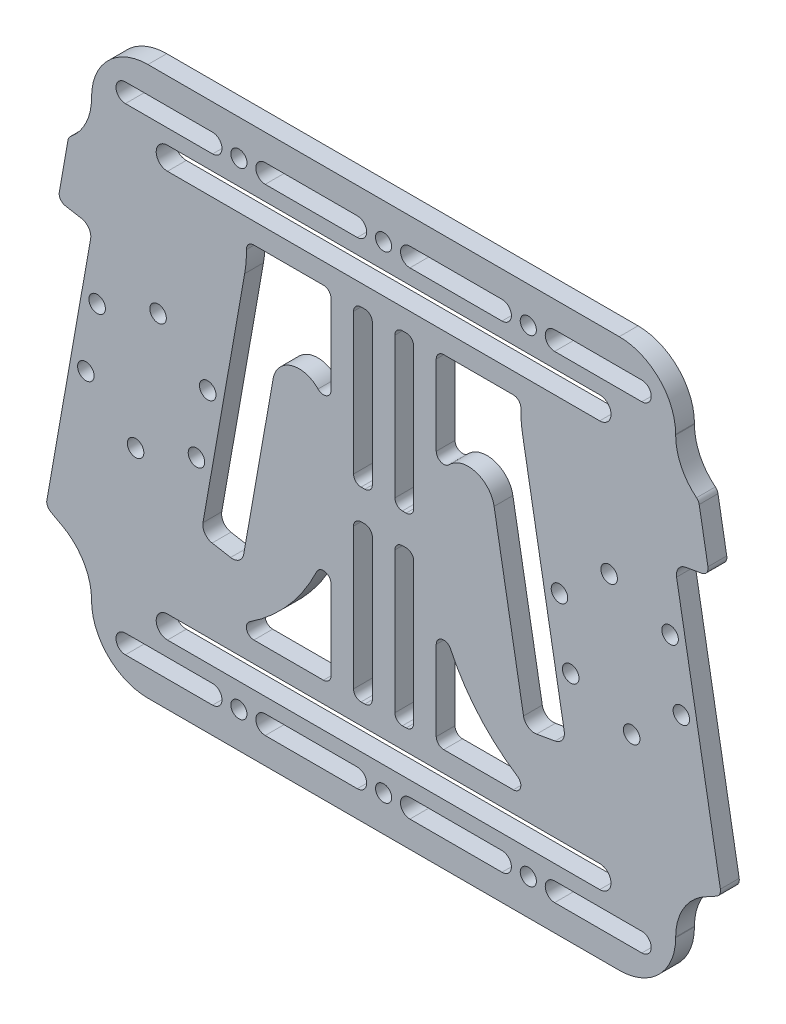
SolidWorks part; units mm, degrees
ref_plane "前视基准面" through (0, 0, 0) normal (0, 0, 1) x (1, 0, 0)
ref_plane "上视基准面" through (0, 0, 0) normal (0, 1, 0) x (1, 0, 0)
ref_plane "右视基准面" through (0, 0, 0) normal (1, 0, 0) x (0, 0, -1)
other "Configuration Table"
sketch "草图1" plane through (0, 0, 0) normal (0, 0, 1) x (1, 0, 0)
  line L0 (0, 0) -> (126, 0) construction
  line L1 (0, 86) -> (126, 86)
  line L2 (0, -86) -> (126, -86)
  line L3 (63, 86) -> (63, -86) construction
  arc A0 (0, 86) -> (0, -86) centre (0, 0) ccw
  arc A1 (126, -86) -> (126, 86) centre (126, 0) ccw
  circle A2 centre (0, 0) radius 44.5 construction
  circle A3 centre (126, 0) radius 44.5 construction
  circle A4 centre (0, 0) radius 42.5 construction
  circle A5 centre (126, 0) radius 42.5 construction
  circle A6 centre (0, 44.5) radius 1.9
  circle A7 centre (31.4663, 31.4663) radius 1.9
  circle A8 centre (44.5, 0) radius 1.9
  circle A9 centre (31.4663, -31.4663) radius 1.9
  circle A10 centre (0, -44.5) radius 1.9
  circle A11 centre (-31.4663, -31.4663) radius 1.9
  circle A12 centre (-44.5, 0) radius 1.9
  circle A13 centre (-31.4663, 31.4663) radius 1.9
  circle A14 centre (-42.5, 0) radius 1.9
  circle A15 centre (42.5, 0) radius 1.9
  circle A16 centre (168.5, 0) radius 1.9
  circle A17 centre (83.5, 0) radius 1.9
  circle A18 centre (94.5337, -31.4663) radius 1.9
  circle A19 centre (126, -44.5) radius 1.9
  circle A20 centre (157.4663, -31.4663) radius 1.9
  circle A21 centre (94.5337, 31.4663) radius 1.9
  circle A22 centre (126, 44.5) radius 1.9
  circle A23 centre (157.4663, 31.4663) radius 1.9
  circle A24 centre (0, 0) radius 31
  circle A25 centre (126, 0) radius 31
  circle A26 centre (126, 42.5) radius 1.9
  circle A27 centre (126, -42.5) radius 1.9
  circle A28 centre (0, -42.5) radius 1.9
  circle A29 centre (0, 42.5) radius 1.9
  circle A30 centre (170.5, 0) radius 1.9
  circle A31 centre (81.5, 0) radius 1.9
  point P3 (63, 0)
  point P33 (0, 0)
  dimension "D1" = 86
  dimension "D3" = 89
  dimension "D4" = 89
  dimension "D5" = 85
  dimension "D6" = 85
  dimension "D7" = 3.8
  dimension "D10" = 3.8
  dimension "D11" = 62
  dimension "D2" = 126
  dimension "D9" = 45
  dimension "D8" = 8
extrude "凸台-拉伸1" add sketch "草图1" along normal blind 5 contours L2 A1 L1 A0 A25 A24 A22 A20 A18 A16 A15 A8 A14 A12 A13 A11 A10 A9 A7 A6 A17 A19 A21 A23 | A15 A8 | A14 A12 region at (63, 0, 0) region at (45.068, 0, 0) region at (-45.068, 0, 0)
sketch "草图3" plane through (0, 0, 5) normal (0, 0, 1) x (1, 0, 0)
  line L0 (13, 41) -> (113, 41)
  line L1 (63, 86) -> (63, -86) construction
  line L2 (13, 41) -> (13, 86)
  line L3 (113, 41) -> (113, 86)
  line L4 (13, 63.5) -> (113, 63.5) construction
  line L5 (0, -86) -> (126, -86)
  line L6 (-86, 0) -> (212, 0) construction
  line L7 (126, 86) -> (0, 86)
  line L9 (0, -86) -> (126, -86)
  line L11 (126, 86) -> (0, 86)
  circle A0 centre (63, 63.5) radius 2.15
  circle A1 centre (101.5, 63.5) radius 2.15
  circle A2 centre (24.5, 63.5) radius 2.15
  circle A3 centre (101.5, -63.5) radius 2.15
  circle A4 centre (63, -63.5) radius 2.15
  circle A5 centre (24.5, -63.5) radius 2.15
  arc A8 (0, 86) -> (0, -86) centre (0, 0) ccw
  arc A12 (126, -86) -> (126, 86) centre (126, 0) ccw
  arc A16 (0, 86) -> (0, -86) centre (0, 0) ccw
  arc A20 (126, -86) -> (126, 86) centre (126, 0) ccw
  dimension "D4" = 4.3
  dimension "D6" = 4.3
  dimension "D2" = 45
  dimension "D3" = 100
  dimension "D5" = 77
  dimension "D1" = 0
extrude "切除-拉伸2" cut sketch "草图3" against normal blind 366 contours A2 | A0 | A1 | A5 | A4 | A3 region at (63, 63.5, 5) region at (101.5, 63.5, 5) region at (24.5, 63.5, 5) region at (101.5, -63.5, 5) region at (63, -63.5, 5) region at (24.5, -63.5, 5)
sketch "草图4" plane through (0, 0, 5) normal (0, 0, 1) x (1, 0, 0)
  line L0 (-15.1381, 73) -> (141.1381, 73)
  line L1 (63, 86) -> (63, -86) construction
  line L2 (0, -86) -> (126, -86)
  line L3 (126, 86) -> (0, 86)
  line L4 (0, -86) -> (126, -86)
  line L5 (126, 86) -> (0, 86)
  line L6 (-86, 0) -> (212, 0) construction
  line L7 (-15.1381, 73) -> (-64, 32)
  line L8 (-64, 32) -> (-64, -32)
  line L9 (-15.1381, -73) -> (141.1381, -73)
  line L10 (-15.1381, -73) -> (-64, -32)
  line L11 (141.1381, -73) -> (190, -32)
  line L12 (141.1381, 73) -> (190, 32)
  line L13 (190, 32) -> (190, -32)
  circle A0 centre (63, 63.5) radius 2.15 construction
  arc A2 (126, -86) -> (126, 86) centre (126, 0) ccw
  arc A3 (0, 86) -> (0, -86) centre (0, 0) ccw
  arc A4 (126, -86) -> (126, 86) centre (126, 0) ccw
  arc A5 (0, 86) -> (0, -86) centre (0, 0) ccw
  point P20 (-64, 0)
  dimension "D2" = 9.5
  dimension "D3" = 140
  dimension "D4" = 22
  dimension "D5" = 32
  dimension "D1" = 0
extrude "切除-拉伸3" cut sketch "草图4" against normal blind 366 contours L4 A4 L5 A5 | L11 L13 L12 L0 L7 L8 L10 L9
fillet "圆角2" radius 20 4 edges at (-15.1381, -73, 2.5) (141.1381, -73, 2.5) (141.1381, 73, 2.5) (-15.1381, 73, 2.5)
fillet "圆角3" radius 35 4 edges at (190, -32, 2.5) (190, 32, 2.5) (-64, -32, 2.5) (-64, 32, 2.5)
sketch "草图8" plane through (0, 0, 5) normal (0, 0, 1) x (1, 0, 0)
  line L2 (126, 86) -> (0, 86)
  line L3 (0, -86) -> (126, -86)
  line L4 (126, 86) -> (0, 86)
  line L5 (0, -86) -> (126, -86)
  arc A0 (169.5, -1.6155) -> (169.5, 1.6155) centre (170.5, 0) ccw construction
  circle A1 centre (0, 44.5) radius 1.9
  circle A2 centre (0, 44.5) radius 1.9
  circle A3 centre (-42.5, 0) radius 1.9
  arc A4 (126, -86) -> (126, 86) centre (126, 0) ccw
  arc A5 (0, 86) -> (0, -86) centre (0, 0) ccw
  arc A6 (126, -86) -> (126, 86) centre (126, 0) ccw
  arc A7 (0, 86) -> (0, -86) centre (0, 0) ccw
  circle A8 centre (-42.5, 0) radius 1.9
  circle A9 centre (-44.5, 0) radius 1.9
  circle A10 centre (-44.5, 0) radius 1.9
  circle A11 centre (-31.4663, -31.4663) radius 1.9
  circle A12 centre (-31.4663, -31.4663) radius 1.9
  circle A13 centre (0, -44.5) radius 1.9
  circle A14 centre (0, -44.5) radius 1.9
  circle A15 centre (31.4663, -31.4663) radius 1.9
  circle A16 centre (31.4663, -31.4663) radius 1.9
  circle A17 centre (44.5, 0) radius 1.9
  circle A18 centre (44.5, 0) radius 1.9
  circle A19 centre (31.4663, 31.4663) radius 1.9
  circle A20 centre (31.4663, 31.4663) radius 1.9
  circle A21 centre (157.4663, -31.4663) radius 1.9
  circle A22 centre (157.4663, -31.4663) radius 1.9
  circle A23 centre (126, -44.5) radius 1.9
  circle A24 centre (126, -44.5) radius 1.9
  circle A25 centre (94.5337, -31.4663) radius 1.9
  circle A26 centre (94.5337, -31.4663) radius 1.9
  circle A27 centre (83.5, 0) radius 1.9
  circle A28 centre (83.5, 0) radius 1.9
  circle A29 centre (168.5, 0) radius 1.9
  circle A30 centre (168.5, 0) radius 1.9
  circle A31 centre (42.5, 0) radius 1.9
  circle A32 centre (42.5, 0) radius 1.9
  circle A33 centre (-31.4663, 31.4663) radius 1.9
  circle A34 centre (-31.4663, 31.4663) radius 1.9
  circle A35 centre (0, -42.5) radius 1.9
  circle A36 centre (0, -42.5) radius 1.9
  circle A37 centre (126, -42.5) radius 1.9
  circle A38 centre (126, -42.5) radius 1.9
  circle A39 centre (126, 42.5) radius 1.9
  circle A40 centre (126, 42.5) radius 1.9
  circle A41 centre (126, 0) radius 31
  circle A42 centre (126, 0) radius 31
  circle A43 centre (0, 0) radius 31
  circle A44 centre (0, 0) radius 31
  circle A45 centre (157.4663, 31.4663) radius 1.9
  circle A46 centre (157.4663, 31.4663) radius 1.9
  circle A47 centre (126, 44.5) radius 1.9
  circle A48 centre (126, 44.5) radius 1.9
  circle A49 centre (94.5337, 31.4663) radius 1.9
  circle A50 centre (94.5337, 31.4663) radius 1.9
  circle A51 centre (0, 42.5) radius 1.9
  circle A52 centre (0, 42.5) radius 1.9
  arc A53 (82.5, 1.6155) -> (82.5, -1.6155) centre (81.5, 0) ccw construction
  arc A54 (169.5, -1.6155) -> (169.5, 1.6155) centre (170.5, 0) ccw
  arc A55 (82.5, 1.6155) -> (82.5, -1.6155) centre (81.5, 0) ccw
  circle A56 centre (81.5, 0) radius 1.9
  circle A57 centre (170.5, 0) radius 1.9
  dimension "D1" = 0
  dimension "D2" = 0
  dimension "D3" = 0
  dimension "D4" = 0
  dimension "D5" = 0
  dimension "D6" = 0
  dimension "D7" = 0
  dimension "D8" = 0
  dimension "D9" = 0
  dimension "D10" = 0
  dimension "D11" = 0
  dimension "D12" = 0
  dimension "D13" = 0
  dimension "D14" = 0
  dimension "D15" = 0
  dimension "D16" = 0
  dimension "D17" = 0
  dimension "D18" = 0
  dimension "D19" = 0
  dimension "D20" = 0
  dimension "D21" = 0
  dimension "D22" = 0
  dimension "D23" = 0
  dimension "D24" = 0
  dimension "D25" = 0
extrude "凸台-拉伸5" add sketch "草图8" against normal blind 5 contours A52 A2 | A36 A14 | A18 A32 | A10 A8 | A40 A48 | A38 A24 | A57 A30 | A56 A28 region at (0, 45.068, 5) region at (-41.932, 0, 5) region at (0, -45.068, 5) region at (41.932, 0, 5) region at (126, -45.068, 5) region at (84.068, 0, 5) region at (167.932, 0, 5) region at (126, 45.068, 5)
sketch "草图9" plane through (0, 0, 5) normal (0, 0, 1) x (1, 0, 0)
  line L2 (126, 86) -> (0, 86)
  line L3 (0, -86) -> (126, -86)
  line L4 (126, 86) -> (0, 86)
  line L5 (0, -86) -> (126, -86)
  arc A0 (169.5, -1.6155) -> (169.5, 1.6155) centre (170.5, 0) ccw construction
  circle A1 centre (-42.5, 0) radius 1.9
  circle A2 centre (-42.5, 0) radius 1.9
  circle A3 centre (0, 44.5) radius 1.9
  circle A4 centre (0, 44.5) radius 1.9
  circle A5 centre (31.4663, 31.4663) radius 1.9
  arc A6 (0, 86) -> (0, -86) centre (0, 0) ccw
  arc A7 (126, -86) -> (126, 86) centre (126, 0) ccw
  arc A8 (0, 86) -> (0, -86) centre (0, 0) ccw
  arc A9 (126, -86) -> (126, 86) centre (126, 0) ccw
  circle A10 centre (31.4663, 31.4663) radius 1.9
  circle A11 centre (44.5, 0) radius 1.9
  circle A12 centre (44.5, 0) radius 1.9
  circle A13 centre (31.4663, -31.4663) radius 1.9
  circle A14 centre (31.4663, -31.4663) radius 1.9
  circle A15 centre (0, -44.5) radius 1.9
  circle A16 centre (0, -44.5) radius 1.9
  circle A17 centre (-31.4663, -31.4663) radius 1.9
  circle A18 centre (-31.4663, -31.4663) radius 1.9
  circle A19 centre (-44.5, 0) radius 1.9
  circle A20 centre (-44.5, 0) radius 1.9
  circle A21 centre (168.5, 0) radius 1.9
  circle A22 centre (168.5, 0) radius 1.9
  circle A23 centre (83.5, 0) radius 1.9
  circle A24 centre (83.5, 0) radius 1.9
  circle A25 centre (94.5337, -31.4663) radius 1.9
  circle A26 centre (94.5337, -31.4663) radius 1.9
  circle A27 centre (126, -44.5) radius 1.9
  circle A28 centre (126, -44.5) radius 1.9
  circle A29 centre (157.4663, -31.4663) radius 1.9
  circle A30 centre (157.4663, -31.4663) radius 1.9
  circle A31 centre (126, 42.5) radius 1.9
  circle A32 centre (126, 42.5) radius 1.9
  circle A33 centre (126, -42.5) radius 1.9
  circle A34 centre (126, -42.5) radius 1.9
  circle A35 centre (0, -42.5) radius 1.9
  circle A36 centre (0, -42.5) radius 1.9
  circle A37 centre (-31.4663, 31.4663) radius 1.9
  circle A38 centre (-31.4663, 31.4663) radius 1.9
  circle A39 centre (42.5, 0) radius 1.9
  circle A40 centre (42.5, 0) radius 1.9
  circle A41 centre (0, 42.5) radius 1.9
  circle A42 centre (0, 42.5) radius 1.9
  circle A43 centre (94.5337, 31.4663) radius 1.9
  circle A44 centre (94.5337, 31.4663) radius 1.9
  circle A45 centre (126, 44.5) radius 1.9
  circle A46 centre (126, 44.5) radius 1.9
  circle A47 centre (157.4663, 31.4663) radius 1.9
  circle A48 centre (157.4663, 31.4663) radius 1.9
  circle A49 centre (0, 0) radius 31
  circle A50 centre (0, 0) radius 31
  circle A51 centre (126, 0) radius 31
  circle A52 centre (126, 0) radius 31
  circle A53 centre (170.5, 0) radius 1.9
  circle A54 centre (170.5, 0) radius 1.9
  circle A55 centre (81.5, 0) radius 1.9
  circle A56 centre (81.5, 0) radius 1.9
  arc A57 (82.5, 1.6155) -> (82.5, -1.6155) centre (81.5, 0) ccw construction
  arc A58 (169.5, -1.6155) -> (169.5, 1.6155) centre (170.5, 0) ccw
  arc A59 (82.5, 1.6155) -> (82.5, -1.6155) centre (81.5, 0) ccw
  dimension "D1" = 0
  dimension "D2" = 0
  dimension "D3" = 0
  dimension "D4" = 0
  dimension "D5" = 0
  dimension "D6" = 0
  dimension "D7" = 0
  dimension "D8" = 0
  dimension "D9" = 0
  dimension "D10" = 0
  dimension "D11" = 0
  dimension "D12" = 0
  dimension "D13" = 0
  dimension "D14" = 0
  dimension "D15" = 0
  dimension "D16" = 0
  dimension "D17" = 0
  dimension "D18" = 0
  dimension "D19" = 0
  dimension "D20" = 0
  dimension "D21" = 0
  dimension "D22" = 0
  dimension "D23" = 0
  dimension "D24" = 0
  dimension "D25" = 0
  dimension "D26" = 0
  dimension "D27" = 0
extrude "切除-拉伸6" cut sketch "草图9" against normal blind 5 contours A20 A2 | A12 A40 region at (-41.932, 0, 5) region at (41.932, 0, 5)
sketch "草图11" plane through (0, 0, 0) normal (0, 0, -1) x (-1, 0, 0)
  line L0 (-63, 73) -> (-63, -73) construction
  line L1 (-140.6991, 71.7939) -> (-140.6991, 47.7905)
  line L2 (-190, 0) -> (64, 0) construction
  line L3 (14.6991, 71.7939) -> (14.6991, 47.7905)
  line L4 (14.6991, -71.7939) -> (14.6991, -47.7905)
  line L5 (-140.6991, -71.7939) -> (-140.6991, -47.7905)
  line L8 (-190, 15.6792) -> (-190, -15.6792)
  line L9 (-177.4976, -42.4908) -> (-146.7145, -68.3209)
  line L10 (-133.8587, -73) -> (7.8587, -73)
  line L11 (20.7145, -68.3209) -> (51.4976, -42.4908)
  line L12 (64, -15.6792) -> (64, 15.6792)
  line L13 (51.4976, 42.4908) -> (20.7145, 68.3209)
  line L14 (7.8587, 73) -> (-133.8587, 73)
  line L15 (-146.7145, 68.3209) -> (-177.4976, 42.4908)
  line L16 (-190, 15.6792) -> (-190, -15.6792)
  line L17 (-177.4976, -42.4908) -> (-146.7145, -68.3209)
  line L18 (-133.8587, -73) -> (7.8587, -73)
  line L19 (20.7145, -68.3209) -> (51.4976, -42.4908)
  line L20 (64, -15.6792) -> (64, 15.6792)
  line L21 (51.4976, 42.4908) -> (20.7145, 68.3209)
  line L22 (7.8587, 73) -> (-133.8587, 73)
  line L23 (-146.7145, 68.3209) -> (-177.4976, 42.4908)
  circle A0 centre (-126, 0) radius 50
  circle A1 centre (0, 0) radius 50
  arc A8 (-190, -15.6792) -> (-177.4976, -42.4908) centre (-155, -15.6792) ccw
  arc A9 (-146.7145, -68.3209) -> (-133.8587, -73) centre (-133.8587, -53) ccw
  arc A10 (7.8587, -73) -> (20.7145, -68.3209) centre (7.8587, -53) ccw
  arc A11 (51.4976, -42.4908) -> (64, -15.6792) centre (29, -15.6792) ccw
  arc A12 (64, 15.6792) -> (51.4976, 42.4908) centre (29, 15.6792) ccw
  arc A13 (20.7145, 68.3209) -> (7.8587, 73) centre (7.8587, 53) ccw
  arc A14 (-133.8587, 73) -> (-146.7145, 68.3209) centre (-133.8587, 53) ccw
  arc A15 (-177.4976, 42.4908) -> (-190, 15.6792) centre (-155, 15.6792) ccw
  arc A16 (-190, -15.6792) -> (-177.4976, -42.4908) centre (-155, -15.6792) ccw
  arc A17 (-146.7145, -68.3209) -> (-133.8587, -73) centre (-133.8587, -53) ccw
  arc A18 (7.8587, -73) -> (20.7145, -68.3209) centre (7.8587, -53) ccw
  arc A19 (51.4976, -42.4908) -> (64, -15.6792) centre (29, -15.6792) ccw
  arc A20 (64, 15.6792) -> (51.4976, 42.4908) centre (29, 15.6792) ccw
  arc A21 (20.7145, 68.3209) -> (7.8587, 73) centre (7.8587, 53) ccw
  arc A22 (-133.8587, 73) -> (-146.7145, 68.3209) centre (-133.8587, 53) ccw
  arc A23 (-177.4976, 42.4908) -> (-190, 15.6792) centre (-155, 15.6792) ccw
  dimension "D2" = 100
  dimension "D1" = 0
extrude "切除-拉伸7" cut sketch "草图11" against normal blind 5 contours L23 A23 L16 A16 L17 A17 L5 A0 L1 A22 | L21 A21 L3 A1 L4 A18 L19 A19 L20 A20 region at (142.2173, 59.7922, 0) region at (-17.0996, 69.0057, 0)
fillet "圆角6" radius 15 4 edges at (140.6991, 71.7939, 2.5) (-14.6991, 71.7939, 2.5) (140.6991, -71.7939, 2.5) (-14.6991, -71.7939, 2.5)
sketch "草图14" plane through (0, 0, 5) normal (0, 0, 1) x (1, 0, 0)
  line L0 (24.5, 63.5) -> (101.3352, 63.5) construction
  line L1 (-5.6991, 63.5) -> (17.5, 63.5) construction
  line L2 (-5.6991, 66) -> (17.5, 66)
  line L3 (-5.6991, 61) -> (17.5, 61)
  line L4 (31.5, 63.5) -> (56, 63.5) construction
  line L5 (31.5, 66) -> (56, 66)
  line L6 (140.6991, 47.7905) -> (140.6991, 58)
  line L7 (125.6991, 73) -> (0.3009, 73)
  line L8 (-14.6991, 58) -> (-14.6991, 47.7905)
  line L9 (-14.6991, -47.7905) -> (-14.6991, -58)
  line L10 (0.3009, -73) -> (125.6991, -73)
  line L11 (140.6991, -58) -> (140.6991, -47.7905)
  line L12 (140.6991, 47.7905) -> (140.6991, 58)
  line L13 (125.6991, 73) -> (0.3009, 73)
  line L14 (-14.6991, 58) -> (-14.6991, 47.7905)
  line L15 (-14.6991, -47.7905) -> (-14.6991, -58)
  line L16 (0.3009, -73) -> (125.6991, -73)
  line L17 (140.6991, -58) -> (140.6991, -47.7905)
  line L18 (31.5, 61) -> (56, 61)
  line L19 (94.5, 63.5) -> (70, 63.5) construction
  line L22 (94.5, 66) -> (70, 66)
  line L25 (63, 73) -> (63, -73) construction
  line L26 (94.5, 61) -> (70, 61)
  line L27 (131.6991, 63.5) -> (108.5, 63.5) construction
  line L28 (131.6991, 66) -> (108.5, 66)
  line L29 (131.6991, 61) -> (108.5, 61)
  line L30 (5.5, 54) -> (120.5, 54) construction
  line L31 (5.5, 57) -> (120.5, 57)
  line L32 (5.5, 51) -> (120.5, 51)
  circle A0 centre (24.5, 63.5) radius 2.15 construction
  circle A1 centre (24.5, 63.5) radius 2.15
  arc A2 (-5.6991, 66) -> (-5.6991, 61) centre (-5.6991, 63.5) ccw
  arc A3 (17.5, 61) -> (17.5, 66) centre (17.5, 63.5) ccw
  arc A4 (31.5, 66) -> (31.5, 61) centre (31.5, 63.5) ccw
  arc A5 (56, 61) -> (56, 66) centre (56, 63.5) ccw
  arc A10 (140.6991, 58) -> (125.6991, 73) centre (125.6991, 58) ccw
  arc A11 (0.3009, 73) -> (-14.6991, 58) centre (0.3009, 58) ccw
  arc A13 (-14.6991, 47.7905) -> (-14.6991, -47.7905) centre (0, 0) ccw
  arc A15 (-14.6991, -58) -> (0.3009, -73) centre (0.3009, -58) ccw
  arc A16 (125.6991, -73) -> (140.6991, -58) centre (125.6991, -58) ccw
  arc A20 (140.6991, 58) -> (125.6991, 73) centre (125.6991, 58) ccw
  arc A21 (0.3009, 73) -> (-14.6991, 58) centre (0.3009, 58) ccw
  arc A25 (-14.6991, -58) -> (0.3009, -73) centre (0.3009, -58) ccw
  arc A26 (125.6991, -73) -> (140.6991, -58) centre (125.6991, -58) ccw
  circle A30 centre (63, 63.5) radius 2.15 construction
  arc A31 (94.5, 66) -> (94.5, 61) centre (94.5, 63.5) cw
  arc A32 (70, 61) -> (70, 66) centre (70, 63.5) cw
  arc A33 (131.6991, 66) -> (131.6991, 61) centre (131.6991, 63.5) cw
  arc A34 (108.5, 61) -> (108.5, 66) centre (108.5, 63.5) cw
  arc A35 (5.5, 57) -> (5.5, 51) centre (5.5, 54) ccw
  arc A36 (120.5, 51) -> (120.5, 57) centre (120.5, 54) ccw
  arc A42 (-14.6991, 47.7905) -> (-14.6991, -47.7905) centre (0, 0) ccw
  arc A43 (140.6991, -47.7905) -> (140.6991, 47.7905) centre (126, 0) ccw
  arc A44 (140.6991, -47.7905) -> (140.6991, 47.7905) centre (126, 0) ccw
  point P23 (5.9004, 63.5)
  point P37 (43.75, 63.5)
  point P46 (63, 54)
  point P52 (82.25, 63.5)
  point P59 (120.0996, 63.5)
  dimension "D2" = 9
  dimension "D7" = 7
  dimension "D8" = 3
  dimension "D10" = 115
  dimension "D3" = 7
  dimension "D4" = 7
  dimension "D5" = 7
  dimension "D6" = 7
  dimension "D9" = 4
  dimension "D1" = 0
extrude "切除-拉伸8" cut sketch "草图14" against normal blind 10 contours L3 A3 L2 A2 | L32 A36 L31 A35 | L18 A5 L5 A4 | L22 A32 L26 A31 | L28 A34 L29 A33
sketch "草图5" plane through (0, 0, 5) normal (0, 0, 1) x (1, 0, 0)
  line L0 (63, 73) -> (63, -73) construction
  line L1 (55, 45.5) -> (55, 4)
  line L2 (-64, 0) -> (190.7132, 0) construction
  line L3 (46.633, 4) -> (80.5073, 4)
  line L4 (71, 45.5) -> (71, 4)
  line L5 (49.8397, -4) -> (76.1603, -4)
  line L6 (5.5, 51) -> (120.5, 51) construction
  line L7 (5.5, 51) -> (120.5, 51)
  line L24 (60, 45.5) -> (60, 4)
  line L25 (77, 45.5) -> (77, 4)
  line L26 (49, 45.5) -> (49, 4)
  line L27 (66, 45.5) -> (66, 4)
  line L30 (20.7304, -45.5) -> (105.2696, -45.5)
  line L31 (77, -45.5) -> (77, -4)
  line L32 (71, -45.5) -> (71, -4)
  line L33 (50, 4) -> (49.8397, 4)
  line L34 (76, 4) -> (76.1603, 4)
  line L35 (66, -45.5) -> (66, -4)
  line L36 (60, -45.5) -> (60, -4)
  line L37 (50, -4) -> (49.8397, -4)
  line L38 (76, -4) -> (76.1603, -4)
  line L39 (55, -45.5) -> (55, -4)
  line L40 (49, -45.5) -> (49, -4)
  line L43 (49.8397, -4) -> (76.1603, -4)
  line L47 (20.7304, 45.5) -> (105.2696, 45.5)
  circle A0 centre (126, 0) radius 50
  circle A1 centre (0, 0) radius 50
  circle A2 centre (0, 0) radius 31 construction
  circle A3 centre (126, 0) radius 31 construction
  circle A4 centre (0, 0) radius 31
  circle A5 centre (126, 0) radius 31
  dimension "D2" = 100
  dimension "D3" = 5.5
  dimension "D4" = 4
  dimension "D5" = 3
  dimension "D6" = 6
  dimension "D1" = 5
extrude "切除-拉伸11" cut sketch "草图5" against normal blind 10 contours A1 L26 L47 | L47 L1 L3 L24 | L47 L27 L3 L4 | A0 L47 L25 | L35 L30 L32 L5 | L39 L30 L36 L5 | A0 L31 L30 | A1 L30 L40 region at (57.5, 24.75, 5) region at (41.0688, 35.9214, 5) region at (68.5, 24.75, 5) region at (41.0688, -35.9214, 5) region at (84.9312, 35.9214, 5) region at (57.5, -24.75, 5) region at (68.5, -24.75, 5) region at (84.9312, -35.9214, 5)
fillet "圆角8" radius 2 28 edges at (71, 45.5, 2.5) (71, 4, 2.5) (66, 4, 2.5) (66, 45.5, 2.5) (60, 45.5, 2.5) (55, 45.5, 2.5) (60, 4, 2.5) (55, 4, 2.5) (71, -45.5, 2.5) (66, -45.5, 2.5) (71, -4, 2.5) (66, -4, 2.5) (60, -4, 2.5) (55, -4, 2.5) (60, -45.5, 2.5) (55, -45.5, 2.5) (49, 45.5, 2.5) (49, -45.5, 2.5) (77, -45.5, 2.5) (105.2696, -45.5, 2.5) (20.7304, -45.5, 2.5) (49, -9.9499, 2.5) (77, -9.9499, 2.5) (77, 9.9499, 2.5) (105.2696, 45.5, 2.5) (77, 45.5, 2.5) (49, 9.9499, 2.5) (20.7304, 45.5, 2.5)
mirror "镜向1" about plane through (0, 0, 0) normal (0, 1, 0) of "切除-拉伸8"
sketch "草图15" plane through (0, 0, 5) normal (0, 0, 1) x (1, 0, 0)
  line L0 (63, 73) -> (63, -73) construction
  line L1 (0, 0) -> (-17.7948, 42.9604) construction
  line L2 (0, 0) -> (0, 40) construction
  line L6 (140.6991, 47.7905) -> (140.6991, 58)
  line L7 (125.6991, 73) -> (0.3009, 73)
  line L8 (-14.6991, 58) -> (-14.6991, 47.7905)
  line L9 (-14.6991, -47.7905) -> (-14.6991, -58)
  line L10 (0.3009, -73) -> (125.6991, -73)
  line L11 (140.6991, -58) -> (140.6991, -47.7905)
  line L12 (140.6991, 47.7905) -> (140.6991, 58)
  line L13 (125.6991, 73) -> (0.3009, 73)
  line L14 (-14.6991, 58) -> (-14.6991, 47.7905)
  line L15 (-14.6991, -47.7905) -> (-14.6991, -58)
  line L16 (0.3009, -73) -> (125.6991, -73)
  line L17 (140.6991, -58) -> (140.6991, -47.7905)
  circle A0 centre (0, 0) radius 31 construction
  circle A1 centre (0, 0) radius 31
  circle A2 centre (126, 0) radius 31 construction
  circle A3 centre (126, 0) radius 31
  circle A4 centre (0, 0) radius 42.5 construction
  circle A5 centre (0, 0) radius 46.5
  circle A6 centre (0, 0) radius 40
  arc A10 (140.6991, 58) -> (125.6991, 73) centre (125.6991, 58) ccw
  arc A11 (0.3009, 73) -> (-14.6991, 58) centre (0.3009, 58) ccw
  arc A13 (-14.6991, 47.7905) -> (-14.6991, -47.7905) centre (0, 0) ccw
  arc A15 (-14.6991, -58) -> (0.3009, -73) centre (0.3009, -58) ccw
  arc A16 (125.6991, -73) -> (140.6991, -58) centre (125.6991, -58) ccw
  arc A20 (140.6991, 58) -> (125.6991, 73) centre (125.6991, 58) ccw
  arc A21 (0.3009, 73) -> (-14.6991, 58) centre (0.3009, 58) ccw
  arc A25 (-14.6991, -58) -> (0.3009, -73) centre (0.3009, -58) ccw
  arc A26 (125.6991, -73) -> (140.6991, -58) centre (125.6991, -58) ccw
  circle A30 centre (-22.919, 36.6781) radius 3.25
  circle A31 centre (-9.7291, 42.1415) radius 3.25
  circle A36 centre (22.919, -36.6781) radius 3.25
  circle A37 centre (9.7291, -42.1415) radius 3.25
  circle A38 centre (43.2237, 1.5094) radius 3.25
  circle A39 centre (41.3602, -12.6451) radius 3.25
  circle A40 centre (20.3046, 38.1875) radius 3.25
  circle A41 centre (31.631, 29.4964) radius 3.25
  circle A42 centre (9.7291, 42.1415) radius 3.25
  circle A43 centre (22.919, 36.6781) radius 3.25
  circle A44 centre (36.6781, 22.919) radius 3.25
  circle A45 centre (42.1415, 9.7291) radius 3.25
  circle A46 centre (42.1415, -9.7291) radius 3.25
  circle A47 centre (36.6781, -22.919) radius 3.25
  circle A48 centre (-9.7291, -42.1415) radius 3.25
  circle A49 centre (-22.919, -36.6781) radius 3.25
  circle A50 centre (-36.6781, -22.919) radius 3.25
  circle A51 centre (-42.1415, -9.7291) radius 3.25
  circle A52 centre (-42.1415, 9.7291) radius 3.25
  circle A53 centre (-36.6781, 22.919) radius 3.25
  circle A54 centre (168.1415, -9.7291) radius 3.25
  circle A55 centre (162.6781, -22.919) radius 3.25
  circle A56 centre (148.919, -36.6781) radius 3.25
  circle A57 centre (135.7291, -42.1415) radius 3.25
  circle A58 centre (116.2709, -42.1415) radius 3.25
  circle A59 centre (103.081, -36.6781) radius 3.25
  circle A60 centre (89.3219, -22.919) radius 3.25
  circle A61 centre (83.8585, -9.7291) radius 3.25
  circle A62 centre (83.8585, 9.7291) radius 3.25
  circle A63 centre (89.3219, 22.919) radius 3.25
  circle A64 centre (103.081, 36.6781) radius 3.25
  circle A65 centre (116.2709, 42.1415) radius 3.25
  circle A66 centre (135.7291, 42.1415) radius 3.25
  circle A67 centre (148.919, 36.6781) radius 3.25
  circle A68 centre (162.6781, 22.919) radius 3.25
  circle A69 centre (168.1415, 9.7291) radius 3.25
  circle A70 centre (126, 0) radius 46.5
  circle A71 centre (126, 0) radius 40
  arc A77 (-14.6991, 47.7905) -> (-14.6991, -47.7905) centre (0, 0) ccw
  arc A78 (140.6991, -47.7905) -> (140.6991, 47.7905) centre (126, 0) ccw
  arc A79 (140.6991, -47.7905) -> (140.6991, 47.7905) centre (126, 0) ccw
  point P57 (0, 0)
  point P66 (0, 0)
  point P70 (0, 0)
  point P76 (0, 0)
  dimension "D2" = 93
  dimension "D3" = 80
  dimension "D4" = 19
  dimension "D5" = 22.5
  dimension "D6" = 4
  dimension "D7" = 2
  dimension "D8" = 2
  dimension "D1" = 0
  dimension "D9" = 2
sketch "草图16" plane through (0, 0, 5) normal (0, 0, 1) x (1, 0, 0)
  line L2 (126, 86) -> (0, 86)
  line L3 (0, -86) -> (126, -86)
  line L4 (126, 86) -> (0, 86)
  line L5 (0, -86) -> (126, -86)
  circle A1 centre (0, 44.5) radius 1.9
  circle A2 centre (0, 44.5) radius 1.9
  circle A3 centre (-42.5, 0) radius 1.9
  arc A4 (126, -86) -> (126, 86) centre (126, 0) ccw
  arc A5 (0, 86) -> (0, -86) centre (0, 0) ccw
  arc A6 (126, -86) -> (126, 86) centre (126, 0) ccw
  arc A7 (0, 86) -> (0, -86) centre (0, 0) ccw
  circle A8 centre (-42.5, 0) radius 1.9
  circle A9 centre (-44.5, 0) radius 1.9
  circle A10 centre (-44.5, 0) radius 1.9
  circle A11 centre (-31.4663, -31.4663) radius 1.9
  circle A12 centre (-31.4663, -31.4663) radius 1.9
  circle A13 centre (0, -44.5) radius 1.9
  circle A14 centre (0, -44.5) radius 1.9
  circle A15 centre (31.4663, -31.4663) radius 1.9
  circle A16 centre (31.4663, -31.4663) radius 1.9
  circle A17 centre (44.5, 0) radius 1.9
  circle A18 centre (44.5, 0) radius 1.9
  circle A19 centre (31.4663, 31.4663) radius 1.9
  circle A20 centre (31.4663, 31.4663) radius 1.9
  circle A21 centre (157.4663, -31.4663) radius 1.9
  circle A22 centre (157.4663, -31.4663) radius 1.9
  circle A23 centre (126, -44.5) radius 1.9
  circle A24 centre (126, -44.5) radius 1.9
  circle A25 centre (94.5337, -31.4663) radius 1.9
  circle A26 centre (94.5337, -31.4663) radius 1.9
  circle A27 centre (83.5, 0) radius 1.9
  circle A28 centre (83.5, 0) radius 1.9
  circle A29 centre (168.5, 0) radius 1.9
  circle A30 centre (168.5, 0) radius 1.9
  circle A31 centre (42.5, 0) radius 1.9
  circle A32 centre (42.5, 0) radius 1.9
  circle A33 centre (-31.4663, 31.4663) radius 1.9
  circle A34 centre (-31.4663, 31.4663) radius 1.9
  circle A35 centre (0, -42.5) radius 1.9
  circle A36 centre (0, -42.5) radius 1.9
  circle A37 centre (126, -42.5) radius 1.9
  circle A38 centre (126, -42.5) radius 1.9
  circle A39 centre (126, 42.5) radius 1.9
  circle A40 centre (126, 42.5) radius 1.9
  circle A41 centre (126, 0) radius 31
  circle A42 centre (126, 0) radius 31
  circle A43 centre (0, 0) radius 31
  circle A44 centre (0, 0) radius 31
  circle A45 centre (157.4663, 31.4663) radius 1.9
  circle A46 centre (157.4663, 31.4663) radius 1.9
  circle A47 centre (126, 44.5) radius 1.9
  circle A48 centre (126, 44.5) radius 1.9
  circle A49 centre (94.5337, 31.4663) radius 1.9
  circle A50 centre (94.5337, 31.4663) radius 1.9
  circle A51 centre (81.5, 0) radius 1.9
  circle A52 centre (81.5, 0) radius 1.9
  circle A53 centre (170.5, 0) radius 1.9
  circle A54 centre (170.5, 0) radius 1.9
  circle A55 centre (0, 42.5) radius 1.9
  circle A56 centre (0, 42.5) radius 1.9
  dimension "D1" = 0
  dimension "D2" = 0
  dimension "D3" = 0
  dimension "D4" = 0
  dimension "D5" = 0
  dimension "D6" = 0
  dimension "D7" = 0
  dimension "D8" = 0
  dimension "D9" = 0
  dimension "D10" = 0
  dimension "D11" = 0
  dimension "D12" = 0
  dimension "D13" = 0
  dimension "D14" = 0
  dimension "D15" = 0
  dimension "D16" = 0
  dimension "D17" = 0
  dimension "D18" = 0
  dimension "D19" = 0
  dimension "D20" = 0
  dimension "D21" = 0
  dimension "D22" = 0
  dimension "D23" = 0
  dimension "D24" = 0
  dimension "D25" = 0
  dimension "D26" = 0
  dimension "D27" = 0
extrude "切除-拉伸14" cut sketch "草图16" against normal blind 10 contours A32 A18 | A8 A10 region at (-45.068, 0, 5) region at (45.068, 0, 5)
sketch "草图17" plane through (0, 0, 5) normal (0, 0, 1) x (1, 0, 0)
  line L2 (126, 86) -> (0, 86)
  line L3 (0, -86) -> (126, -86)
  line L4 (126, 86) -> (0, 86)
  line L5 (0, -86) -> (126, -86)
  circle A1 centre (-42.5, 0) radius 1.9
  circle A2 centre (-42.5, 0) radius 1.9
  circle A3 centre (0, 44.5) radius 1.9
  circle A4 centre (0, 44.5) radius 1.9
  circle A5 centre (31.4663, 31.4663) radius 1.9
  arc A6 (0, 86) -> (0, -86) centre (0, 0) ccw
  arc A7 (126, -86) -> (126, 86) centre (126, 0) ccw
  arc A8 (0, 86) -> (0, -86) centre (0, 0) ccw
  arc A9 (126, -86) -> (126, 86) centre (126, 0) ccw
  circle A10 centre (31.4663, 31.4663) radius 1.9
  circle A11 centre (44.5, 0) radius 1.9
  circle A12 centre (44.5, 0) radius 1.9
  circle A13 centre (31.4663, -31.4663) radius 1.9
  circle A14 centre (31.4663, -31.4663) radius 1.9
  circle A15 centre (0, -44.5) radius 1.9
  circle A16 centre (0, -44.5) radius 1.9
  circle A17 centre (-31.4663, -31.4663) radius 1.9
  circle A18 centre (-31.4663, -31.4663) radius 1.9
  circle A19 centre (-44.5, 0) radius 1.9
  circle A20 centre (-44.5, 0) radius 1.9
  circle A21 centre (168.5, 0) radius 1.9
  circle A22 centre (168.5, 0) radius 1.9
  circle A23 centre (83.5, 0) radius 1.9
  circle A24 centre (83.5, 0) radius 1.9
  circle A25 centre (94.5337, -31.4663) radius 1.9
  circle A26 centre (94.5337, -31.4663) radius 1.9
  circle A27 centre (126, -44.5) radius 1.9
  circle A28 centre (126, -44.5) radius 1.9
  circle A29 centre (157.4663, -31.4663) radius 1.9
  circle A30 centre (157.4663, -31.4663) radius 1.9
  circle A31 centre (126, 42.5) radius 1.9
  circle A32 centre (126, 42.5) radius 1.9
  circle A33 centre (126, -42.5) radius 1.9
  circle A34 centre (126, -42.5) radius 1.9
  circle A35 centre (0, -42.5) radius 1.9
  circle A36 centre (0, -42.5) radius 1.9
  circle A37 centre (-31.4663, 31.4663) radius 1.9
  circle A38 centre (-31.4663, 31.4663) radius 1.9
  circle A39 centre (42.5, 0) radius 1.9
  circle A40 centre (42.5, 0) radius 1.9
  circle A41 centre (81.5, 0) radius 1.9
  circle A42 centre (81.5, 0) radius 1.9
  circle A43 centre (94.5337, 31.4663) radius 1.9
  circle A44 centre (94.5337, 31.4663) radius 1.9
  circle A45 centre (126, 44.5) radius 1.9
  circle A46 centre (126, 44.5) radius 1.9
  circle A47 centre (157.4663, 31.4663) radius 1.9
  circle A48 centre (157.4663, 31.4663) radius 1.9
  circle A49 centre (0, 0) radius 31
  circle A50 centre (0, 0) radius 31
  circle A51 centre (126, 0) radius 31
  circle A52 centre (126, 0) radius 31
  circle A53 centre (0, 42.5) radius 1.9
  circle A54 centre (0, 42.5) radius 1.9
  circle A55 centre (170.5, 0) radius 1.9
  circle A56 centre (170.5, 0) radius 1.9
  dimension "D1" = 0
  dimension "D2" = 0
  dimension "D3" = 0
  dimension "D4" = 0
  dimension "D5" = 0
  dimension "D6" = 0
  dimension "D7" = 0
  dimension "D8" = 0
  dimension "D9" = 0
  dimension "D10" = 0
  dimension "D11" = 0
  dimension "D12" = 0
  dimension "D13" = 0
  dimension "D14" = 0
  dimension "D15" = 0
  dimension "D16" = 0
  dimension "D17" = 0
  dimension "D18" = 0
  dimension "D19" = 0
  dimension "D20" = 0
  dimension "D21" = 0
  dimension "D22" = 0
  dimension "D23" = 0
  dimension "D24" = 0
  dimension "D25" = 0
  dimension "D26" = 0
  dimension "D27" = 0
extrude "凸台-拉伸6" add sketch "草图17" against normal blind 5 contours A20 A2 | A12 A40 region at (-41.932, 0, 5) region at (41.932, 0, 5)
sketch "草图19" plane through (0, 0, 5) normal (0, 0, 1) x (1, 0, 0)
  circle A0 centre (126, -42.5) radius 1.9 construction
  circle A1 centre (157.4663, -31.4663) radius 1.9 construction
  circle A2 centre (170.5, 0) radius 1.9 construction
  circle A3 centre (157.4663, 31.4663) radius 1.9 construction
  circle A4 centre (126, 42.5) radius 1.9 construction
  circle A5 centre (94.5337, 31.4663) radius 1.9 construction
  circle A6 centre (81.5, 0) radius 1.9 construction
  circle A7 centre (94.5337, -31.4663) radius 1.9 construction
  circle A8 centre (-44.5, 0) radius 1.9 construction
  circle A9 centre (-31.4663, 31.4663) radius 1.9 construction
  circle A10 centre (0, 42.5) radius 1.9 construction
  circle A11 centre (31.4663, 31.4663) radius 1.9 construction
  circle A12 centre (44.5, 0) radius 1.9 construction
  circle A13 centre (31.4663, -31.4663) radius 1.9 construction
  circle A14 centre (0, -42.5) radius 1.9 construction
  circle A15 centre (-31.4663, -31.4663) radius 1.9 construction
  circle A16 centre (126, -42.5) radius 1.9
  circle A17 centre (157.4663, -31.4663) radius 1.9
  circle A18 centre (170.5, 0) radius 1.9
  circle A19 centre (157.4663, 31.4663) radius 1.9
  circle A20 centre (126, 42.5) radius 1.9
  circle A21 centre (94.5337, 31.4663) radius 1.9
  circle A22 centre (81.5, 0) radius 1.9
  circle A23 centre (94.5337, -31.4663) radius 1.9
  circle A24 centre (-44.5, 0) radius 1.9
  circle A25 centre (-31.4663, 31.4663) radius 1.9
  circle A26 centre (0, 42.5) radius 1.9
  circle A27 centre (31.4663, 31.4663) radius 1.9
  circle A28 centre (44.5, 0) radius 1.9
  circle A29 centre (31.4663, -31.4663) radius 1.9
  circle A30 centre (0, -42.5) radius 1.9
  circle A31 centre (-31.4663, -31.4663) radius 1.9
  circle A32 centre (0, 0) radius 31 construction
  circle A33 centre (0, 0) radius 31
  circle A34 centre (126, 0) radius 31 construction
  circle A35 centre (126, 0) radius 31
extrude "凸台-拉伸7" add sketch "草图19" against normal blind 5
sketch "草图20" plane through (0, 0, 5) normal (0, 0, 1) x (1, 0, 0)
  line L0 (0, 17.25) -> (0, -17.25) construction
  line L1 (2.9954, 16.9879) -> (-2.9954, -16.9879)
  line L2 (63, 51) -> (63, -51) construction
  line L3 (5.5, 51) -> (120.5, 51) construction
  line L4 (5.5, -51) -> (120.5, -51) construction
  circle A0 centre (0, 0) radius 17.25 construction
  circle A1 centre (2.9954, 16.9879) radius 2.2
  circle A2 centre (16.2097, 5.8998) radius 2.2
  circle A3 centre (13.2143, -11.0881) radius 2.2
  circle A4 centre (-2.9954, -16.9879) radius 2.2
  circle A5 centre (-16.2097, -5.8998) radius 2.2
  circle A6 centre (-13.2143, 11.0881) radius 2.2
  circle A7 centre (128.9954, -16.9879) radius 2.2
  circle A8 centre (112.7857, -11.0881) radius 2.2
  circle A9 centre (109.7903, 5.8998) radius 2.2
  circle A10 centre (123.0046, 16.9879) radius 2.2
  circle A11 centre (139.2143, 11.0881) radius 2.2
  circle A12 centre (142.2097, -5.8998) radius 2.2
  point P20 (0, 0)
  dimension "D1" = 34.5
  dimension "D2" = 10
  dimension "D3" = 4.4
  dimension "D4" = 6
extrude "切除-拉伸15" cut sketch "草图20" against normal blind 5 contours A1 | A2 | A6 | A5 | A4 | A3 | A8 | A9 | A10 | A11 | A12 | A7 region at (-1.3578, -15.6138, 5) region at (1.6213, 18.6256, 5) region at (16.2097, 5.8998, 5) region at (13.2143, -11.0881, 5) region at (-16.2097, -5.8998, 5) region at (-13.2143, 11.0881, 5) region at (128.9954, -16.9879, 5) region at (112.7857, -11.0881, 5) region at (109.7903, 5.8998, 5) region at (123.0046, 16.9879, 5) region at (139.2143, 11.0881, 5) region at (142.2097, -5.8998, 5)
sketch "草图21" plane through (0, 0, 5) normal (0, 0, 1) x (1, 0, 0)
  line L0 (2.9954, 16.9879) -> (-2.9954, -16.9879) construction
  line L1 (-18.8098, 3.3167) -> (18.8098, -3.3167) construction
  line L2 (-14.4252, 28.1831) -> (-23.1944, -21.5497)
  line L3 (-14.4252, 28.1831) -> (-25.2581, 30.0932)
  line L4 (-25.2581, 30.0932) -> (-34.0273, -19.6396)
  line L5 (-34.0273, -19.6396) -> (-23.1944, -21.5497)
  line L6 (34.0273, 19.6396) -> (25.2581, -30.0932)
  line L7 (23.1944, 21.5497) -> (34.0273, 19.6396)
  line L8 (23.1944, 21.5497) -> (14.4252, -28.1831)
  line L9 (25.2581, -30.0932) -> (14.4252, -28.1831)
  line L10 (63, 51) -> (63, -51) construction
  line L11 (5.5, 51) -> (120.5, 51) construction
  line L12 (5.5, -51) -> (120.5, -51) construction
  line L13 (102.8056, 21.5497) -> (91.9727, 19.6396)
  line L14 (102.8056, 21.5497) -> (111.5748, -28.1831)
  line L15 (100.7419, -30.0932) -> (111.5748, -28.1831)
  line L16 (91.9727, 19.6396) -> (100.7419, -30.0932)
  line L17 (151.2581, 30.0932) -> (160.0273, -19.6396)
  line L18 (140.4252, 28.1831) -> (151.2581, 30.0932)
  line L19 (140.4252, 28.1831) -> (149.1944, -21.5497)
  line L20 (160.0273, -19.6396) -> (149.1944, -21.5497)
  dimension "D1" = 38.2
  dimension "D2" = 50.5
  dimension "D3" = 11
extrude "切除-拉伸16" cut sketch "草图21" against normal blind 39
fillet "圆角9" radius 3 16 edges at (160.0273, -19.6396, 2.5) (149.1944, -21.5497, 2.5) (151.2581, 30.0932, 2.5) (140.4252, 28.1831, 2.5) (111.5748, -28.1831, 2.5) (100.7419, -30.0932, 2.5) (102.8056, 21.5497, 2.5) (91.9727, 19.6396, 2.5) (23.1944, 21.5497, 2.5) (34.0273, 19.6396, 2.5) (25.2581, -30.0932, 2.5) (14.4252, -28.1831, 2.5) (-23.1944, -21.5497, 2.5) (-34.0273, -19.6396, 2.5) (-14.4252, 28.1831, 2.5) (-25.2581, 30.0932, 2.5)
sketch "草图22" plane through (0, 0, 5) normal (0, 0, 1) x (1, 0, 0)
  line L0 (25.779, -27.1388) -> (33.5064, 16.6852) construction
  line L1 (22.6735, 18.5953) -> (14.9462, -25.2287) construction
  line L2 (17.3796, -28.704) -> (22.3037, -29.5723) construction
  line L3 (25.779, -27.1388) -> (33.5064, 16.6852)
  line L4 (22.6735, 18.5953) -> (14.9462, -25.2287)
  line L5 (17.3796, -28.704) -> (22.3037, -29.5723)
  line L6 (22.6735, 18.5953) -> (27.0423, 43.3719)
  line L7 (27.0423, 43.3719) -> (37.8752, 41.4618)
  line L8 (37.8752, 41.4618) -> (33.5064, 16.6852)
  arc A0 (22.3037, -29.5723) -> (25.779, -27.1388) centre (22.8246, -26.6178) ccw construction
  arc A1 (14.9462, -25.2287) -> (17.3796, -28.704) centre (17.9006, -25.7496) ccw construction
  arc A2 (22.3037, -29.5723) -> (25.779, -27.1388) centre (22.8246, -26.6178) ccw
  arc A3 (14.9462, -25.2287) -> (17.3796, -28.704) centre (17.9006, -25.7496) ccw
extrude "切除-拉伸17" cut sketch "草图22" against normal blind 10 contours L8 L3 A2 L5 A3 L4 L6 L7
ref_plane "基准面1" through (63, 0, 0) normal (1, 0, 0) x (0, 0, -1)
mirror "镜向2" about plane through (63, 0, 0) normal (1, 0, 0) of "切除-拉伸17"
fillet "圆角10" radius 30 2 edges at (26.8607, 42.3419, 2.5) (99.1393, 42.3419, 2.5)
fillet "圆角11" radius 7 2 edges at (36.5756, 34.0914, 2.5) (89.4244, 34.0914, 2.5)
sketch "草图23" plane through (0, 0, 5) normal (0, 0, 1) x (1, 0, 0)
  line L0 (-25.779, 27.1388) -> (-33.5064, -16.6852) construction
  line L1 (-25.779, 27.1388) -> (-33.5064, -16.6852)
  line L2 (-32.2908, -9.7915) -> (-49.5423, -6.7496)
  line L3 (-14.6991, 47.7905) -> (-17.3796, 28.704)
  line L5 (-32.2908, -9.7915) -> (-17.3796, 28.704)
  line L6 (-31.0729, -20.1605) -> (-26.1489, -21.0288) construction
  line L7 (-31.0729, -20.1605) -> (-26.1489, -21.0288)
  line L12 (140.6991, 47.7905) -> (140.6991, 58)
  line L13 (125.6991, 73) -> (0.3009, 73)
  line L14 (-14.6991, 58) -> (-14.6991, 47.7905)
  line L15 (-14.6991, -47.7905) -> (-14.6991, -58)
  line L16 (0.3009, -73) -> (125.6991, -73)
  line L17 (140.6991, -58) -> (140.6991, -47.7905)
  line L18 (140.6991, 47.7905) -> (140.6991, 58)
  line L19 (125.6991, 73) -> (0.3009, 73)
  line L20 (-14.6991, 58) -> (-14.6991, 47.7905)
  line L21 (-14.6991, -47.7905) -> (-14.6991, -58)
  line L22 (0.3009, -73) -> (125.6991, -73)
  line L23 (140.6991, -58) -> (140.6991, -47.7905)
  arc A6 (140.6991, 58) -> (125.6991, 73) centre (125.6991, 58) ccw
  arc A7 (0.3009, 73) -> (-14.6991, 58) centre (0.3009, 58) ccw
  arc A8 (-14.6991, 47.7905) -> (-14.6991, -47.7905) centre (0, 0) ccw
  arc A9 (-14.6991, -58) -> (0.3009, -73) centre (0.3009, -58) ccw
  arc A10 (125.6991, -73) -> (140.6991, -58) centre (125.6991, -58) ccw
  arc A11 (140.6991, -47.7905) -> (140.6991, 47.7905) centre (126, 0) ccw
  arc A12 (140.6991, 58) -> (125.6991, 73) centre (125.6991, 58) ccw
  arc A13 (0.3009, 73) -> (-14.6991, 58) centre (0.3009, 58) ccw
  arc A14 (-14.6991, 47.7905) -> (-14.6991, -47.7905) centre (0, 0) ccw
  arc A15 (-14.6991, -58) -> (0.3009, -73) centre (0.3009, -58) ccw
  arc A16 (125.6991, -73) -> (140.6991, -58) centre (125.6991, -58) ccw
  arc A17 (140.6991, -47.7905) -> (140.6991, 47.7905) centre (126, 0) ccw
  point P8 (-28.6109, -20.5947)
  dimension "D1" = 10
  dimension "D2" = 0
sketch "草图25" plane through (0, 0, 5) normal (0, 0, 1) x (1, 0, 0)
  line L0 (-22.6735, -18.5953) -> (-14.9462, 25.2287) construction
  line L1 (-28.5085, -51.6871) -> (-14.9462, 25.2287)
  line L2 (-25.779, 27.1388) -> (-33.5064, -16.6852) construction
  line L3 (-25.779, 27.1388) -> (-39.2439, -49.224)
  line L4 (-25.779, 27.1388) -> (-14.9462, 25.2287)
  line L5 (-39.2439, -49.224) -> (-28.5085, -51.6871)
  line L6 (140.6991, 47.7905) -> (140.6991, 58)
  line L7 (125.6991, 73) -> (0.3009, 73)
  line L8 (-14.6991, 58) -> (-14.6991, 47.7905)
  line L9 (-14.6991, -47.7905) -> (-14.6991, -58)
  line L10 (0.3009, -73) -> (125.6991, -73)
  line L11 (140.6991, -58) -> (140.6991, -47.7905)
  line L12 (140.6991, 47.7905) -> (140.6991, 58)
  line L13 (125.6991, 73) -> (0.3009, 73)
  line L14 (-14.6991, 58) -> (-14.6991, 47.7905)
  line L15 (-14.6991, -47.7905) -> (-14.6991, -58)
  line L16 (0.3009, -73) -> (125.6991, -73)
  line L17 (140.6991, -58) -> (140.6991, -47.7905)
  arc A6 (140.6991, 58) -> (125.6991, 73) centre (125.6991, 58) ccw
  arc A7 (0.3009, 73) -> (-14.6991, 58) centre (0.3009, 58) ccw
  arc A8 (-14.6991, 47.7905) -> (-14.6991, -47.7905) centre (0, 0) ccw
  arc A9 (-14.6991, -58) -> (0.3009, -73) centre (0.3009, -58) ccw
  arc A10 (125.6991, -73) -> (140.6991, -58) centre (125.6991, -58) ccw
  arc A11 (140.6991, -47.7905) -> (140.6991, 47.7905) centre (126, 0) ccw
  arc A12 (140.6991, 58) -> (125.6991, 73) centre (125.6991, 58) ccw
  arc A13 (0.3009, 73) -> (-14.6991, 58) centre (0.3009, 58) ccw
  arc A14 (-14.6991, 47.7905) -> (-14.6991, -47.7905) centre (0, 0) ccw
  arc A15 (-14.6991, -58) -> (0.3009, -73) centre (0.3009, -58) ccw
  arc A16 (125.6991, -73) -> (140.6991, -58) centre (125.6991, -58) ccw
  arc A17 (140.6991, -47.7905) -> (140.6991, 47.7905) centre (126, 0) ccw
  dimension "D1" = 0
extrude "切除-拉伸21" cut sketch "草图25" against normal blind 10 contours L3 A14 L1 L4 region at (-25.9788, -6.1706, 5)
fillet "圆角15" radius 15 4 edges at (-14.6991, -47.7905, 2.5) (140.6991, -47.7905, 2.5) (140.6991, 47.7905, 2.5) (-14.6991, 47.7905, 2.5)
sketch "草图26" plane through (0, 0, 5) normal (0, 0, 1) x (1, 0, 0)
  line L0 (-26.4736, 23.1996) -> (-42.6741, 26.0561)
  line L9 (-14.6991, 58) -> (-14.6991, 57.8184)
  line L10 (-36.5756, -34.0914) -> (-25.779, 27.1388)
  line L11 (-22.3037, 29.5723) -> (-17.3796, 28.704)
  line L12 (-14.9462, 25.2287) -> (-26.8338, -42.1894)
  line L13 (-14.6991, -57.8184) -> (-14.6991, -58)
  line L14 (0.3009, -73) -> (125.6991, -73)
  line L15 (140.6991, -58) -> (140.6991, -57.8184)
  line L16 (140.6991, 57.8184) -> (140.6991, 58)
  line L17 (125.6991, 73) -> (0.3009, 73)
  line L18 (-14.6991, 58) -> (-14.6991, 57.8184)
  line L19 (-36.5756, -34.0914) -> (-25.779, 27.1388)
  line L20 (-22.3037, 29.5723) -> (-17.3796, 28.704)
  line L21 (-14.9462, 25.2287) -> (-26.8338, -42.1894)
  line L22 (-14.6991, -57.8184) -> (-14.6991, -58)
  line L23 (0.3009, -73) -> (125.6991, -73)
  line L24 (140.6991, -58) -> (140.6991, -57.8184)
  line L25 (140.6991, 57.8184) -> (140.6991, 58)
  line L26 (125.6991, 73) -> (0.3009, 73)
  arc A13 (-22.8455, 44.4757) -> (-14.6991, 57.8184) centre (-29.6991, 57.8184) ccw
  arc A14 (-22.8455, 44.4757) -> (-36.5756, -34.0914) centre (0, 0) ccw
  arc A15 (-22.3037, 29.5723) -> (-25.779, 27.1388) centre (-22.8246, 26.6178) ccw
  arc A16 (-14.9462, 25.2287) -> (-17.3796, 28.704) centre (-17.9006, 25.7496) ccw
  arc A17 (-26.8338, -42.1894) -> (-22.8455, -44.4757) centre (0, 0) ccw
  arc A18 (-14.6991, -57.8184) -> (-22.8455, -44.4757) centre (-29.6991, -57.8184) ccw
  arc A19 (-14.6991, -58) -> (0.3009, -73) centre (0.3009, -58) ccw
  arc A20 (125.6991, -73) -> (140.6991, -58) centre (125.6991, -58) ccw
  arc A21 (148.8455, -44.4757) -> (140.6991, -57.8184) centre (155.6991, -57.8184) ccw
  arc A22 (148.8455, -44.4757) -> (148.8455, 44.4757) centre (126, 0) ccw
  arc A23 (140.6991, 57.8184) -> (148.8455, 44.4757) centre (155.6991, 57.8184) ccw
  arc A24 (140.6991, 58) -> (125.6991, 73) centre (125.6991, 58) ccw
  arc A25 (0.3009, 73) -> (-14.6991, 58) centre (0.3009, 58) ccw
  arc A26 (-22.8455, 44.4757) -> (-14.6991, 57.8184) centre (-29.6991, 57.8184) ccw
  arc A27 (-22.8455, 44.4757) -> (-36.5756, -34.0914) centre (0, 0) ccw
  arc A28 (-22.3037, 29.5723) -> (-25.779, 27.1388) centre (-22.8246, 26.6178) ccw
  arc A29 (-14.9462, 25.2287) -> (-17.3796, 28.704) centre (-17.9006, 25.7496) ccw
  arc A30 (-26.8338, -42.1894) -> (-22.8455, -44.4757) centre (0, 0) ccw
  arc A31 (-14.6991, -57.8184) -> (-22.8455, -44.4757) centre (-29.6991, -57.8184) ccw
  arc A32 (-14.6991, -58) -> (0.3009, -73) centre (0.3009, -58) ccw
  arc A33 (125.6991, -73) -> (140.6991, -58) centre (125.6991, -58) ccw
  arc A34 (148.8455, -44.4757) -> (140.6991, -57.8184) centre (155.6991, -57.8184) ccw
  arc A35 (148.8455, -44.4757) -> (148.8455, 44.4757) centre (126, 0) ccw
  arc A36 (140.6991, 57.8184) -> (148.8455, 44.4757) centre (155.6991, 57.8184) ccw
  arc A37 (140.6991, 58) -> (125.6991, 73) centre (125.6991, 58) ccw
  arc A38 (0.3009, 73) -> (-14.6991, 58) centre (0.3009, 58) ccw
  dimension "D2" = 7
  dimension "D1" = 0
extrude "切除-拉伸22" cut sketch "草图26" against normal blind 10 contours L0 A27 L19 region at (-39.1956, 0.6252, 5)
mirror "镜向6" about plane through (63, 0, 0) normal (1, 0, 0) of "切除-拉伸21", "切除-拉伸22"
fillet "圆角16" radius 2 2 edges at (-26.4736, 23.1996, 2.5) (152.4736, 23.1996, 2.5)
fillet "圆角17" radius 6 2 edges at (-42.6741, 26.0561, 2.5) (168.6741, 26.0561, 2.5)
fillet "圆角18" radius 2 2 edges at (152.8338, -42.1894, 2.5) (-26.8338, -42.1894, 2.5)
sketch "草图27" plane through (0, 0, 5) normal (0, 0, 1) x (1, 0, 0)
  line L0 (149.6925, 29.4896) -> (146.8305, 45.721)
  line L1 (148.3037, 29.5723) -> (143.3796, 28.704) construction
  line L2 (63, 73) -> (63, -73) construction
  line L3 (-23.6925, 29.4896) -> (-20.8305, 45.721)
  line L16 (152.5981, -40.8527) -> (140.9462, 25.2287)
  line L17 (143.3796, 28.704) -> (148.3037, 29.5723)
  line L18 (151.779, 27.1388) -> (152.1263, 25.1692)
  line L19 (154.4432, 23.5468) -> (158.9874, 24.3481)
  line L20 (140.6991, 57.8184) -> (140.6991, 58)
  line L21 (125.6991, 73) -> (0.3009, 73)
  line L22 (-14.6991, 58) -> (-14.6991, 57.8184)
  line L23 (-32.9874, 24.3481) -> (-28.4432, 23.5468)
  line L24 (-26.1263, 25.1692) -> (-25.779, 27.1388)
  line L25 (-22.3037, 29.5723) -> (-17.3796, 28.704)
  line L26 (-14.9462, 25.2287) -> (-26.5981, -40.8527)
  line L27 (-14.6991, -57.8184) -> (-14.6991, -58)
  line L28 (0.3009, -73) -> (125.6991, -73)
  line L29 (140.6991, -58) -> (140.6991, -57.8184)
  line L30 (152.5981, -40.8527) -> (140.9462, 25.2287)
  line L31 (143.3796, 28.704) -> (148.3037, 29.5723)
  line L32 (151.779, 27.1388) -> (152.1263, 25.1692)
  line L33 (154.4432, 23.5468) -> (158.9874, 24.3481)
  line L34 (140.6991, 57.8184) -> (140.6991, 58)
  line L35 (125.6991, 73) -> (0.3009, 73)
  line L36 (-14.6991, 58) -> (-14.6991, 57.8184)
  line L37 (-32.9874, 24.3481) -> (-28.4432, 23.5468)
  line L38 (-26.1263, 25.1692) -> (-25.779, 27.1388)
  line L39 (-22.3037, 29.5723) -> (-17.3796, 28.704)
  line L40 (-14.9462, 25.2287) -> (-26.5981, -40.8527)
  line L41 (-14.6991, -57.8184) -> (-14.6991, -58)
  line L42 (0.3009, -73) -> (125.6991, -73)
  line L43 (140.6991, -58) -> (140.6991, -57.8184)
  arc A0 (151.779, 27.1388) -> (148.3037, 29.5723) centre (148.8246, 26.6178) ccw construction
  arc A1 (140.6991, 57.8184) -> (148.8455, 44.4757) centre (155.6991, 57.8184) ccw construction
  arc A24 (148.8455, -44.4757) -> (151.6547, -42.9167) centre (126, 0) ccw
  arc A25 (151.6547, -42.9167) -> (152.5981, -40.8527) centre (150.6285, -41.2) ccw
  arc A26 (143.3796, 28.704) -> (140.9462, 25.2287) centre (143.9006, 25.7496) ccw
  arc A27 (151.779, 27.1388) -> (148.3037, 29.5723) centre (148.8246, 26.6178) ccw
  arc A28 (152.1263, 25.1692) -> (154.4432, 23.5468) centre (154.096, 25.5165) ccw
  arc A29 (158.9874, 24.3481) -> (162.3017, 34.3829) centre (157.9455, 30.257) ccw
  arc A30 (162.3017, 34.3829) -> (148.8455, 44.4757) centre (126, 0) ccw
  arc A31 (140.6991, 57.8184) -> (148.8455, 44.4757) centre (155.6991, 57.8184) ccw
  arc A32 (140.6991, 58) -> (125.6991, 73) centre (125.6991, 58) ccw
  arc A33 (0.3009, 73) -> (-14.6991, 58) centre (0.3009, 58) ccw
  arc A34 (-22.8455, 44.4757) -> (-14.6991, 57.8184) centre (-29.6991, 57.8184) ccw
  arc A35 (-22.8455, 44.4757) -> (-36.3017, 34.3829) centre (0, 0) ccw
  arc A36 (-36.3017, 34.3829) -> (-32.9874, 24.3481) centre (-31.9455, 30.257) ccw
  arc A37 (-28.4432, 23.5468) -> (-26.1263, 25.1692) centre (-28.096, 25.5165) ccw
  arc A38 (-22.3037, 29.5723) -> (-25.779, 27.1388) centre (-22.8246, 26.6178) ccw
  arc A39 (-14.9462, 25.2287) -> (-17.3796, 28.704) centre (-17.9006, 25.7496) ccw
  arc A40 (-26.5981, -40.8527) -> (-25.6547, -42.9167) centre (-24.6285, -41.2) ccw
  arc A41 (-25.6547, -42.9167) -> (-22.8455, -44.4757) centre (0, 0) ccw
  arc A42 (-14.6991, -57.8184) -> (-22.8455, -44.4757) centre (-29.6991, -57.8184) ccw
  arc A43 (-14.6991, -58) -> (0.3009, -73) centre (0.3009, -58) ccw
  arc A44 (125.6991, -73) -> (140.6991, -58) centre (125.6991, -58) ccw
  arc A45 (148.8455, -44.4757) -> (140.6991, -57.8184) centre (155.6991, -57.8184) ccw
  arc A46 (148.8455, -44.4757) -> (151.6547, -42.9167) centre (126, 0) ccw
  arc A47 (151.6547, -42.9167) -> (152.5981, -40.8527) centre (150.6285, -41.2) ccw
  arc A48 (143.3796, 28.704) -> (140.9462, 25.2287) centre (143.9006, 25.7496) ccw
  arc A49 (151.779, 27.1388) -> (148.3037, 29.5723) centre (148.8246, 26.6178) ccw
  arc A50 (152.1263, 25.1692) -> (154.4432, 23.5468) centre (154.096, 25.5165) ccw
  arc A51 (158.9874, 24.3481) -> (162.3017, 34.3829) centre (157.9455, 30.257) ccw
  arc A52 (162.3017, 34.3829) -> (148.8455, 44.4757) centre (126, 0) ccw
  arc A53 (140.6991, 57.8184) -> (148.8455, 44.4757) centre (155.6991, 57.8184) ccw
  arc A54 (140.6991, 58) -> (125.6991, 73) centre (125.6991, 58) ccw
  arc A55 (0.3009, 73) -> (-14.6991, 58) centre (0.3009, 58) ccw
  arc A56 (-22.8455, 44.4757) -> (-14.6991, 57.8184) centre (-29.6991, 57.8184) ccw
  arc A57 (-22.8455, 44.4757) -> (-36.3017, 34.3829) centre (0, 0) ccw
  arc A58 (-36.3017, 34.3829) -> (-32.9874, 24.3481) centre (-31.9455, 30.257) ccw
  arc A59 (-28.4432, 23.5468) -> (-26.1263, 25.1692) centre (-28.096, 25.5165) ccw
  arc A60 (-22.3037, 29.5723) -> (-25.779, 27.1388) centre (-22.8246, 26.6178) ccw
  arc A61 (-14.9462, 25.2287) -> (-17.3796, 28.704) centre (-17.9006, 25.7496) ccw
  arc A62 (-26.5981, -40.8527) -> (-25.6547, -42.9167) centre (-24.6285, -41.2) ccw
  arc A63 (-25.6547, -42.9167) -> (-22.8455, -44.4757) centre (0, 0) ccw
  arc A64 (-14.6991, -57.8184) -> (-22.8455, -44.4757) centre (-29.6991, -57.8184) ccw
  arc A65 (-14.6991, -58) -> (0.3009, -73) centre (0.3009, -58) ccw
  arc A66 (125.6991, -73) -> (140.6991, -58) centre (125.6991, -58) ccw
  arc A67 (148.8455, -44.4757) -> (140.6991, -57.8184) centre (155.6991, -57.8184) ccw
  dimension "D1" = 0
extrude "切除-拉伸23" cut sketch "草图27" against normal blind 10 contours A60 L3 A56 A57 A58 L37 A59 L38 | A53 L0 A49 L32 A50 L33 A51 A52 region at (155.187, 33.145, 5) region at (-29.187, 33.145, 5)
fillet "圆角19" radius 2 4 edges at (-20.8305, 45.721, 2.5) (-23.6925, 29.4896, 2.5) (146.8305, 45.721, 2.5) (149.6925, 29.4896, 2.5)
